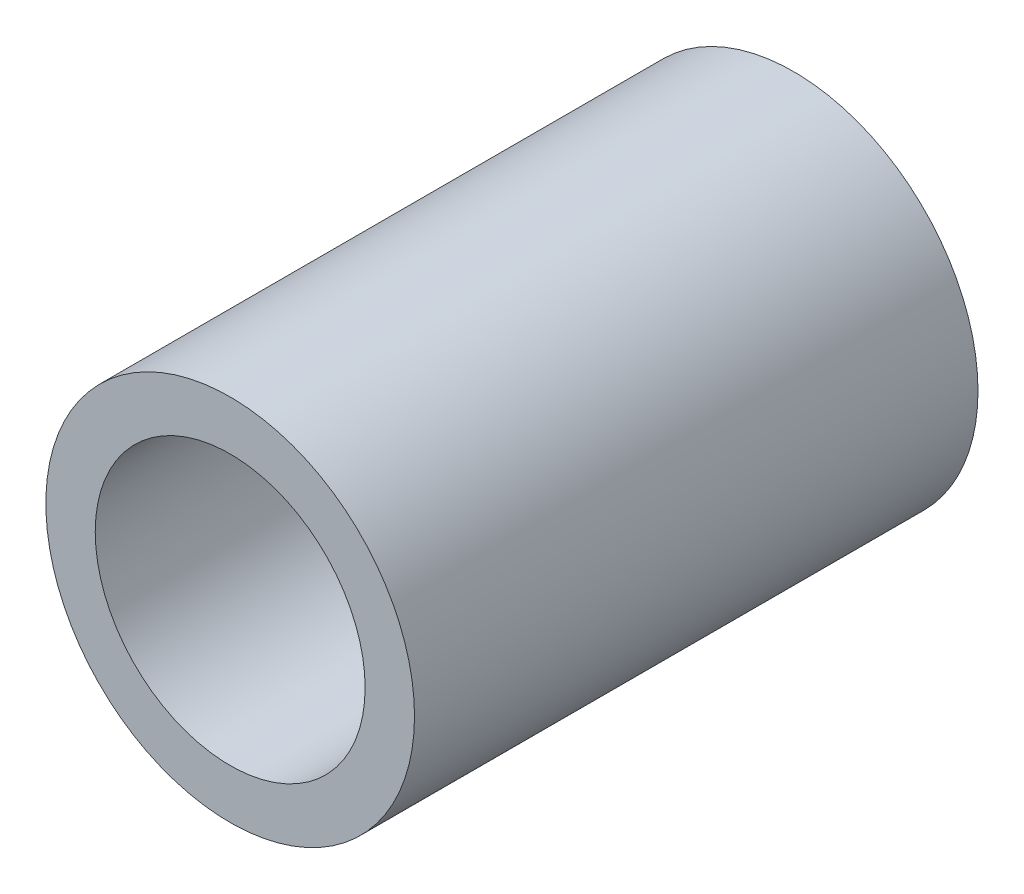
SolidWorks part; units mm, degrees
material "PLA 50%"
ref_plane "Front Plane" through (0, 0, 0) normal (0, 0, 1) x (1, 0, 0)
ref_plane "Top Plane" through (0, 0, 0) normal (0, 1, 0) x (1, 0, 0)
ref_plane "Right Plane" through (0, 0, 0) normal (1, 0, 0) x (0, 0, -1)
ref_axis "X" through (-88.99, 0, 0) along (1, 0, 0)
ref_axis "Y" through (0, 55, 0) along (0, -1, 0)
ref_axis "Z" through (0, 0, -88.99) along (0, 0, 1)
sketch "Sketch1" plane through (0, 0, 0) normal (0, 0, 1) x (1, 0, 0)
  circle A0 centre (0, 0) radius 5.125
  circle A1 centre (0, 0) radius 7
  dimension "D1" = 10.25
  dimension "D2" = 14
extrude "Boss-Extrude1" add sketch "Sketch1" against normal up to surface (21.3988 mm away)
